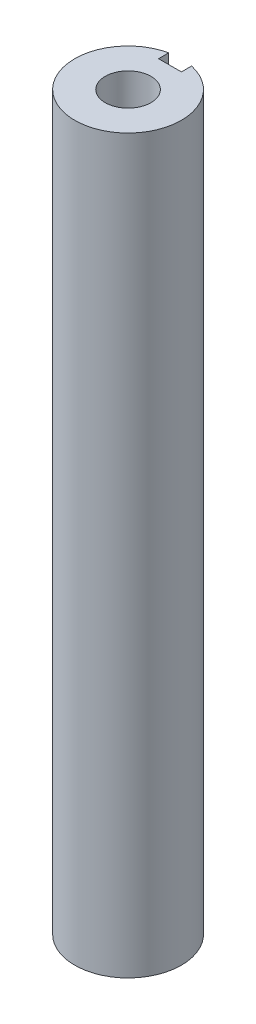
SolidWorks part; units mm, degrees
ref_plane "Front Plane" through (0, 0, 0) normal (0, 0, 1) x (1, 0, 0)
ref_plane "Top Plane" through (0, 0, 0) normal (0, 1, 0) x (1, 0, 0)
ref_plane "Right Plane" through (0, 0, 0) normal (1, 0, 0) x (0, 0, -1)
sketch "Sketch1" plane through (0, 0, 0) normal (0, 1, 0) x (1, 0, 0)
  line L0 (0, 0) -> (0, 74.8181) construction
  line L2 (-2.3813, 10.8544) -> (-2.3813, 8.7312)
  line L3 (-2.3813, 8.7312) -> (2.3813, 8.7312)
  line L4 (2.3813, 10.8544) -> (2.3813, 8.7312)
  line L5 (4.0598, 11.1125) -> (-6.0262, 11.1125) construction
  arc A1 (2.3813, 10.8544) -> (-2.3813, 10.8544) centre (0, 0) cw
  circle A2 centre (0, 0) radius 4.7625
  dimension "D1" = 6.35
  dimension "7/16" = 11.1125
  dimension "D2" = 4.7625
  dimension "D3" = 2.3813
extrude "Shaft" add sketch "Sketch1" along normal blind 152.4
